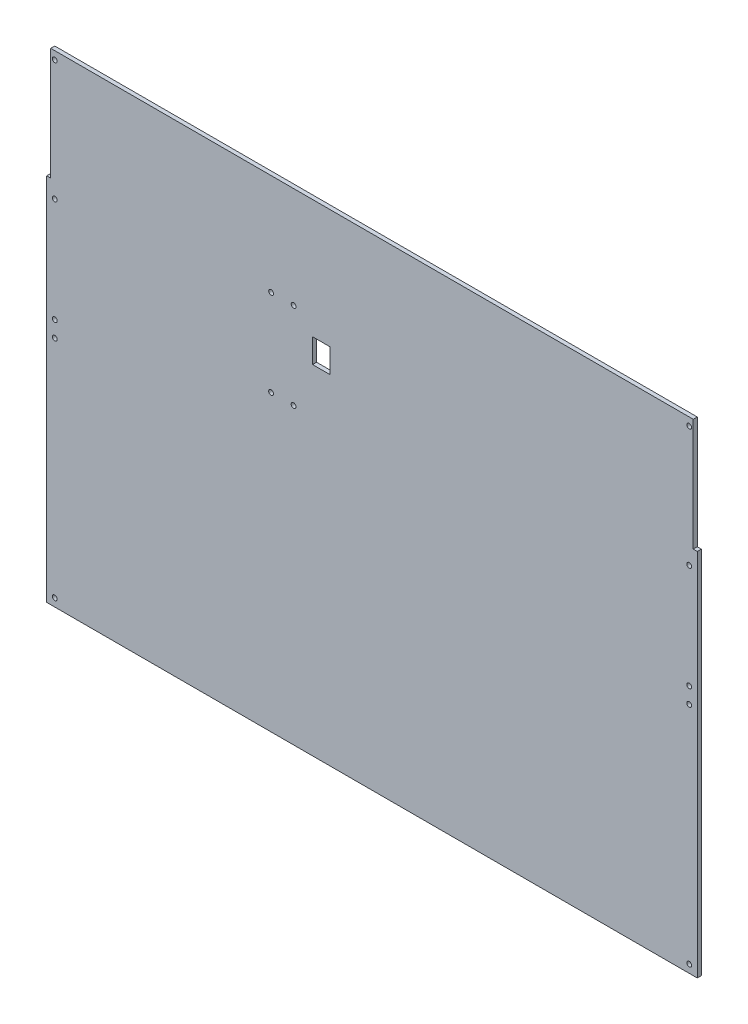
SolidWorks part; units mm, degrees
ref_plane "Front Plane" through (0, 0, 0) normal (0, 0, 1) x (1, 0, 0)
ref_plane "Top Plane" through (0, 0, 0) normal (0, 1, 0) x (1, 0, 0)
ref_plane "Right Plane" through (0, 0, 0) normal (1, 0, 0) x (0, 0, -1)
sketch "Sketch1" plane through (0, 0, 0) normal (0, 0, 1) x (1, 0, 0)
  line L1 (-254, -190.5) -> (254, -190.5)
  line L2 (-254, -190.5) -> (-254, 190.5)
  line L3 (-254, 190.5) -> (254, 190.5)
  line L4 (254, -190.5) -> (254, 190.5)
  line L5 (-254, -190.5) -> (254, 190.5) construction
  line L6 (-254, 190.5) -> (254, -190.5) construction
  point P0 (0, 0)
  dimension "D1" = 508
  dimension "D2" = 381
extrude "Boss-Extrude1" add sketch "Sketch1" along normal blind 3.175
sketch "Sketch3" plane through (0, 0, 3.175) normal (0, 0, 1) x (1, 0, 0)
  line L0 (-254, 190.5) -> (-254, -190.5) construction
  line L1 (-46.99, 77.47) -> (-33.02, 77.47)
  line L2 (-46.99, 77.47) -> (-46.99, 96.52)
  line L3 (-46.99, 96.52) -> (-33.02, 96.52)
  line L4 (-33.02, 77.47) -> (-33.02, 96.52)
  line L5 (254, 190.5) -> (-254, 190.5) construction
  dimension "D1" = 207.01
  dimension "D2" = 13.97
  dimension "D3" = 113.03
  dimension "D4" = 19.05
extrude "Cut-Extrude2" cut sketch "Sketch3" against normal up to surface (3.175 mm away) up to face at (0, 0, 0)
sketch "Sketch2" plane through (0, 0, 3.175) normal (0, 0, 1) x (1, 0, 0)
  line L1 (254, 190.5) -> (-254, 190.5) construction
  line L2 (-254, -190.5) -> (254, -190.5) construction
  line L3 (250.825, 190.5) -> (250.825, -190.5) construction
  line L4 (254, -190.5) -> (254, 190.5) construction
  line L6 (0, 0) -> (0, -50000) construction
  line L8 (-33.02, 96.52) -> (-46.99, 96.52) construction
  line L10 (254, 190.5) -> (-254, 190.5) construction
  circle A2 centre (250.825, 184.15) radius 1.905
  circle A3 centre (250.825, -184.15) radius 1.905
  circle A12 centre (-79.7747, 110.49) radius 1.905
  circle A13 centre (-79.7747, 41.91) radius 1.905
  circle A14 centre (-61.9947, 110.49) radius 1.905
  circle A15 centre (-61.9947, 41.91) radius 1.905
  circle A16 centre (-250.825, 184.15) radius 1.905
  circle A17 centre (-250.825, 88.9) radius 1.905
  circle A18 centre (250.825, 88.9) radius 1.905
  circle A19 centre (250.825, 6.35) radius 1.905
  circle A20 centre (250.825, -6.35) radius 1.905
  circle A21 centre (-250.825, 6.35) radius 1.905
  circle A22 centre (-250.825, -6.35) radius 1.905
  circle A23 centre (-250.825, -184.15) radius 1.905
  point P33 (0, -190.5)
  dimension "D14" = 3.81
  dimension "D12" = 17.78
  dimension "D18" = 3.81
  dimension "D1" = 3.175
  dimension "D5" = 6.35
  dimension "D6" = 6.35
  dimension "D11" = 177.8
  dimension "D13" = 68.58
  dimension "D15" = 15.0047
  dimension "D16" = 13.97
  dimension "D17" = 177.8
  dimension "D19" = 101.6
extrude "Cut-Extrude1" cut sketch "Sketch2" against normal blind 3.175
sketch "Sketch4" plane through (0, 0, 3.175) normal (0, 0, 1) x (1, 0, 0)
  line L0 (254, -190.5) -> (254, 190.5) construction
  line L1 (254, 101.6) -> (257.175, 101.6)
  line L2 (254, 101.6) -> (254, -190.5)
  line L3 (254, -190.5) -> (257.175, -190.5)
  line L4 (257.175, 101.6) -> (257.175, -190.5)
  line L5 (-254, -190.5) -> (254, -190.5) construction
  line L6 (254, 190.5) -> (-254, 190.5) construction
  line L7 (0, 190.5) -> (0, -190.5) construction
  line L8 (-254, -190.5) -> (-257.175, -190.5)
  line L9 (-254, 101.6) -> (-257.175, 101.6)
  line L10 (-254, 101.6) -> (-254, -190.5)
  line L11 (-257.175, 101.6) -> (-257.175, -190.5)
  dimension "D1" = 3.175
  dimension "D2" = 88.9
extrude "Boss-Extrude2" add sketch "Sketch4" against normal blind 3.175
